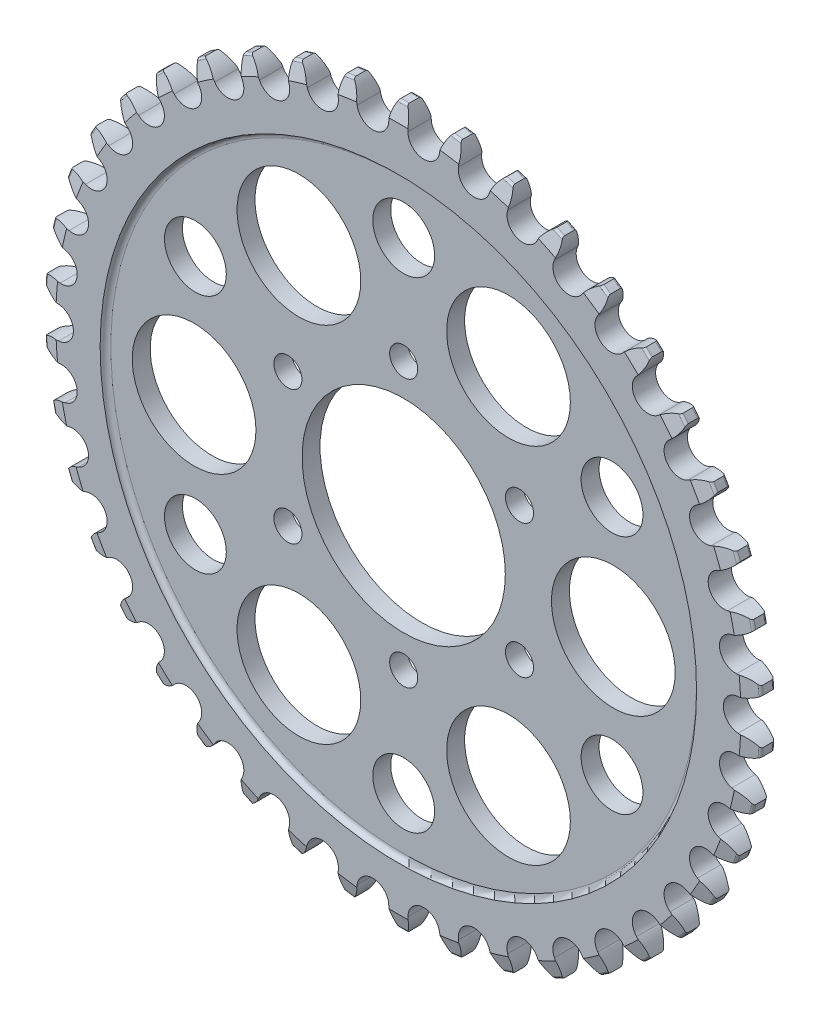
SolidWorks part; units mm, degrees
ref_plane "Front" through (0, 0, 0) normal (0, 0, 1) x (1, 0, 0)
ref_plane "Top" through (0, 0, 0) normal (0, 1, 0) x (1, 0, 0)
ref_plane "Right" through (0, 0, 0) normal (1, 0, 0) x (0, 0, -1)
sketch "Sketch1" plane through (0, 0, 0) normal (0, 0, 1) x (1, 0, 0)
  line L0 (0, 0) -> (0, 165.4268) construction
  line L1 (0, 0) -> (24.4609, 162.2874) construction
  line L2 (0, 0) -> (-25.1185, 166.6504) construction
  line L3 (-9.525, 0) -> (-9.525, 165.4268) construction
  line L4 (9.525, 0) -> (9.525, 163.4542) construction
  line L5 (-9.525, 0) -> (-9.525, 27.2747) construction
  line L6 (9.525, 0) -> (9.525, 27.2747) construction
  line L7 (0, 0) -> (0, 27.2747) construction
  line L8 (9.4186, 1.4196) -> (-15.3101, 165.4838) construction
  line L9 (-9.4186, 1.4196) -> (15.1489, 164.4141) construction
  line L10 (0, 0) -> (11.7596, 78.0201) construction
  line L11 (-9.4186, 1.4196) -> (2.341, 79.4398) construction
  line L12 (9.4186, 1.4196) -> (-9.2498, 125.2762) construction
  line L13 (0, 0) -> (-18.6684, 123.8565) construction
  line L14 (-9.525, 127.1023) -> (9.525, 127.1023) construction
  line L15 (0, 0) -> (60.5367, 104.8526) construction
  line L16 (0, 0) -> (123.9656, 71.5716) construction
  arc A0 (-9.525, 121.1492) -> (-3.5719, 127.1023) centre (-9.525, 127.1023) ccw
  circle A1 centre (0, 0) radius 111.5056
  arc A2 (3.5719, 127.1023) -> (8.6377, 121.2157) centre (9.525, 127.1023) ccw
  arc A3 (0, 136.0913) -> (-3.5719, 127.1023) centre (9.525, 127.1023) ccw
  circle A4 centre (0, 0) radius 101.5056 construction
  arc A5 (3.5719, 127.1023) -> (0, 136.0913) centre (-9.525, 127.1023) ccw
  circle A6 centre (0, 0) radius 38
  circle A7 centre (0, 0) radius 50 construction
  circle A8 centre (0, 50) radius 5.25
  circle A9 centre (0, 0) radius 55.25 construction
  circle A10 centre (39.1889, 67.8772) radius 23.1278
  circle A11 centre (77.8918, 44.9708) radius 11.5639
  circle A12 centre (0, 0) radius 78.3778 construction
  circle A13 centre (43.3013, 25) radius 5.25
  circle A14 centre (78.3778, 0) radius 23.1278
  circle A15 centre (77.8918, -44.9708) radius 11.5639
  circle A16 centre (43.3013, -25) radius 5.25
  circle A17 centre (39.1889, -67.8772) radius 23.1278
  circle A18 centre (0, -89.9417) radius 11.5639
  circle A19 centre (0, -50) radius 5.25
  circle A20 centre (-39.1889, -67.8772) radius 23.1278
  circle A21 centre (-77.8918, -44.9708) radius 11.5639
  circle A22 centre (-43.3013, -25) radius 5.25
  circle A23 centre (-78.3778, 0) radius 23.1278
  circle A24 centre (-77.8918, 44.9708) radius 11.5639
  circle A25 centre (-43.3013, 25) radius 5.25
  circle A26 centre (-39.1889, 67.8772) radius 23.1278
  circle A27 centre (0, 89.9417) radius 11.5639
  arc A28 (8.6377, 121.2157) -> (15.4116, 126.215) centre (9.525, 127.1023) ccw
  arc A29 (20.2834, 134.5713) -> (15.4116, 126.215) centre (28.3622, 124.263) ccw
  arc A30 (22.4756, 125.1503) -> (20.2834, 134.5713) centre (9.525, 127.1023) ccw
  arc A31 (22.4756, 125.1503) -> (26.6075, 118.5744) centre (28.3622, 124.263) ccw
  arc A32 (26.6075, 118.5744) -> (34.0509, 122.5083) centre (28.3622, 124.263) ccw
  arc A33 (40.1136, 130.0452) -> (34.0509, 122.5083) centre (46.5659, 118.648) ccw
  arc A34 (40.8772, 120.4027) -> (40.1136, 130.0452) centre (28.3622, 124.263) ccw
  arc A35 (40.8772, 120.4027) -> (43.9829, 113.2844) centre (46.5659, 118.648) ccw
  arc A36 (43.9829, 113.2844) -> (51.9295, 116.065) centre (46.5659, 118.648) ccw
  arc A37 (59.0478, 122.614) -> (51.9295, 116.065) centre (63.7293, 110.3825) ccw
  arc A38 (58.3658, 112.9654) -> (59.0478, 122.614) centre (46.5659, 118.648) ccw
  arc A39 (58.3658, 112.9654) -> (60.3758, 105.4638) centre (63.7293, 110.3825) ccw
  arc A40 (60.3758, 105.4638) -> (68.648, 107.029) centre (63.7293, 110.3825) ccw
  arc A41 (76.663, 112.4439) -> (68.648, 107.029) centre (79.4692, 99.6512) ccw
  arc A42 (74.5505, 103.0047) -> (76.663, 112.4439) centre (63.7293, 110.3825) ccw
  arc A43 (74.5505, 103.0047) -> (75.42, 95.2873) centre (79.4692, 99.6512) ccw
  arc A44 (75.42, 95.2873) -> (83.8331, 95.6021) centre (79.4692, 99.6512) ccw
  arc A45 (92.5656, 99.762) -> (83.8331, 95.6021) centre (93.4338, 86.6939) ccw
  arc A46 (89.0699, 90.7431) -> (92.5656, 99.762) centre (79.4692, 99.6512) ccw
  arc A47 (89.0699, 90.7431) -> (88.7795, 82.9822) centre (93.4338, 86.6939) ccw
  arc A48 (88.7795, 82.9822) -> (97.1455, 82.0396) centre (93.4338, 86.6939) ccw
  arc A49 (106.4005, 84.8515) -> (97.1455, 82.0396) centre (105.3113, 71.8) ccw
  arc A50 (101.5996, 76.4544) -> (106.4005, 84.8515) centre (93.4338, 86.6939) ccw
  arc A51 (101.5996, 76.4544) -> (100.1558, 68.8235) centre (105.3113, 71.8) ccw
  arc A52 (100.1558, 68.8235) -> (108.2879, 66.6445) centre (105.3113, 71.8) ccw
  arc A53 (117.8585, 68.0457) -> (108.2879, 66.6445) centre (114.8363, 55.3023) ccw
  arc A54 (111.8598, 60.4578) -> (117.8585, 68.0457) centre (105.3113, 71.8) ccw
  arc A55 (111.8598, 60.4578) -> (109.2947, 53.1273) centre (114.8363, 55.3023) ccw
  arc A56 (109.2947, 53.1273) -> (117.0112, 49.7606) centre (114.8363, 55.3023) ccw
  arc A57 (126.6838, 49.7197) -> (117.0112, 49.7606) centre (121.7961, 37.5691) ccw
  arc A58 (119.6211, 43.1107) -> (126.6838, 49.7197) centre (114.8363, 55.3023) ccw
  arc A59 (119.6211, 43.1107) -> (115.9922, 36.2444) centre (121.7961, 37.5691) ccw
  arc A60 (115.9922, 36.2444) -> (123.1208, 31.7652) centre (121.7961, 37.5691) ccw
  arc A61 (132.6792, 30.2832) -> (123.1208, 31.7652) centre (126.0351, 18.9967) ccw
  arc A62 (124.7104, 24.8006) -> (132.6792, 30.2832) centre (121.7961, 37.5691) ccw
  arc A63 (124.7104, 24.8006) -> (120.0986, 18.5519) centre (126.0351, 18.9967) ccw
  arc A64 (120.0986, 18.5519) -> (126.48, 13.0603) centre (126.0351, 18.9967) ccw
  arc A65 (135.7108, 10.1701) -> (126.48, 13.0603) centre (127.4587, 0) ccw
  arc A66 (127.0138, 5.9365) -> (135.7108, 10.1701) centre (126.0351, 18.9967) ccw
  arc A67 (127.0138, 5.9365) -> (121.5222, 0.4449) centre (127.4587, 0) ccw
  arc A68 (121.5222, 0.4449) -> (127.0138, -5.9365) centre (127.4587, 0) ccw
  arc A69 (135.7108, -10.1701) -> (127.0138, -5.9365) centre (126.0351, -18.9967) ccw
  arc A70 (126.48, -13.0603) -> (135.7108, -10.1701) centre (127.4587, 0) ccw
  arc A71 (126.48, -13.0603) -> (120.2312, -17.672) centre (126.0351, -18.9967) ccw
  arc A72 (120.2312, -17.672) -> (124.7104, -24.8006) centre (126.0351, -18.9967) ccw
  arc A73 (132.6792, -30.2832) -> (124.7104, -24.8006) centre (121.7961, -37.5691) ccw
  arc A74 (123.1208, -31.7652) -> (132.6792, -30.2832) centre (126.0351, -18.9967) ccw
  arc A75 (123.1208, -31.7652) -> (116.2545, -35.3942) centre (121.7961, -37.5691) ccw
  arc A76 (116.2545, -35.3942) -> (119.6211, -43.1107) centre (121.7961, -37.5691) ccw
  arc A77 (126.6838, -49.7197) -> (119.6211, -43.1107) centre (114.8363, -55.3023) ccw
  arc A78 (117.0112, -49.7606) -> (126.6838, -49.7197) centre (121.7961, -37.5691) ccw
  arc A79 (117.0112, -49.7606) -> (109.6808, -52.3257) centre (114.8363, -55.3023) ccw
  arc A80 (109.6808, -52.3257) -> (111.8598, -60.4578) centre (114.8363, -55.3023) ccw
  arc A81 (117.8585, -68.0457) -> (111.8598, -60.4578) centre (105.3113, -71.8) ccw
  arc A82 (108.2879, -66.6445) -> (117.8585, -68.0457) centre (114.8363, -55.3023) ccw
  arc A83 (108.2879, -66.6445) -> (100.657, -68.0883) centre (105.3113, -71.8) ccw
  arc A84 (100.657, -68.0883) -> (101.5996, -76.4544) centre (105.3113, -71.8) ccw
  arc A85 (106.4005, -84.8515) -> (101.5996, -76.4544) centre (93.4338, -86.6939) ccw
  arc A86 (97.1455, -82.0396) -> (106.4005, -84.8515) centre (105.3113, -71.8) ccw
  arc A87 (97.1455, -82.0396) -> (89.3847, -82.33) centre (93.4338, -86.6939) ccw
  arc A88 (89.3847, -82.33) -> (89.0699, -90.7431) centre (93.4338, -86.6939) ccw
  arc A89 (92.5656, -99.762) -> (89.0699, -90.7431) centre (79.4692, -99.6512) ccw
  arc A90 (83.8331, -95.6021) -> (92.5656, -99.762) centre (93.4338, -86.6939) ccw
  arc A91 (83.8331, -95.6021) -> (76.1157, -94.7325) centre (79.4692, -99.6512) ccw
  arc A92 (76.1157, -94.7325) -> (74.5505, -103.0047) centre (79.4692, -99.6512) ccw
  arc A93 (76.663, -112.4439) -> (74.5505, -103.0047) centre (63.7293, -110.3825) ccw
  arc A94 (68.648, -107.029) -> (76.663, -112.4439) centre (79.4692, -99.6512) ccw
  arc A95 (68.648, -107.029) -> (61.1464, -105.0189) centre (63.7293, -110.3825) ccw
  arc A96 (61.1464, -105.0189) -> (58.3658, -112.9654) centre (63.7293, -110.3825) ccw
  arc A97 (59.0478, -122.614) -> (58.3658, -112.9654) centre (46.5659, -118.648) ccw
  arc A98 (51.9295, -116.065) -> (59.0478, -122.614) centre (63.7293, -110.3825) ccw
  arc A99 (51.9295, -116.065) -> (44.8112, -112.9593) centre (46.5659, -118.648) ccw
  arc A100 (44.8112, -112.9593) -> (40.8772, -120.4027) centre (46.5659, -118.648) ccw
  arc A101 (40.1136, -130.0452) -> (40.8772, -120.4027) centre (28.3622, -124.263) ccw
  arc A102 (34.0509, -122.5083) -> (40.1136, -130.0452) centre (46.5659, -118.648) ccw
  arc A103 (34.0509, -122.5083) -> (27.475, -118.3764) centre (28.3622, -124.263) ccw
  arc A104 (27.475, -118.3764) -> (22.4756, -125.1503) centre (28.3622, -124.263) ccw
  arc A105 (20.2834, -134.5713) -> (22.4756, -125.1503) centre (9.525, -127.1023) ccw
  arc A106 (15.4116, -126.215) -> (20.2834, -134.5713) centre (28.3622, -124.263) ccw
  arc A107 (15.4116, -126.215) -> (9.525, -121.1492) centre (9.525, -127.1023) ccw
  arc A108 (9.525, -121.1492) -> (3.5719, -127.1023) centre (9.525, -127.1023) ccw
  arc A109 (0, -136.0913) -> (3.5719, -127.1023) centre (-9.525, -127.1023) ccw
  arc A110 (-3.5719, -127.1023) -> (0, -136.0913) centre (9.525, -127.1023) ccw
  arc A111 (-3.5719, -127.1023) -> (-8.6377, -121.2157) centre (-9.525, -127.1023) ccw
  arc A112 (-8.6377, -121.2157) -> (-15.4116, -126.215) centre (-9.525, -127.1023) ccw
  arc A113 (-20.2834, -134.5713) -> (-15.4116, -126.215) centre (-28.3622, -124.263) ccw
  arc A114 (-22.4756, -125.1503) -> (-20.2834, -134.5713) centre (-9.525, -127.1023) ccw
  arc A115 (-22.4756, -125.1503) -> (-26.6075, -118.5744) centre (-28.3622, -124.263) ccw
  arc A116 (-26.6075, -118.5744) -> (-34.0509, -122.5083) centre (-28.3622, -124.263) ccw
  arc A117 (-40.1136, -130.0452) -> (-34.0509, -122.5083) centre (-46.5659, -118.648) ccw
  arc A118 (-40.8772, -120.4027) -> (-40.1136, -130.0452) centre (-28.3622, -124.263) ccw
  arc A119 (-40.8772, -120.4027) -> (-43.9829, -113.2844) centre (-46.5659, -118.648) ccw
  arc A120 (-43.9829, -113.2844) -> (-51.9295, -116.065) centre (-46.5659, -118.648) ccw
  arc A121 (-59.0478, -122.614) -> (-51.9295, -116.065) centre (-63.7293, -110.3825) ccw
  arc A122 (-58.3658, -112.9654) -> (-59.0478, -122.614) centre (-46.5659, -118.648) ccw
  arc A123 (-58.3658, -112.9654) -> (-60.3758, -105.4638) centre (-63.7293, -110.3825) ccw
  arc A124 (-60.3758, -105.4638) -> (-68.648, -107.029) centre (-63.7293, -110.3825) ccw
  arc A125 (-76.663, -112.4439) -> (-68.648, -107.029) centre (-79.4692, -99.6512) ccw
  arc A126 (-74.5505, -103.0047) -> (-76.663, -112.4439) centre (-63.7293, -110.3825) ccw
  arc A127 (-74.5505, -103.0047) -> (-75.42, -95.2873) centre (-79.4692, -99.6512) ccw
  arc A128 (-75.42, -95.2873) -> (-83.8331, -95.6021) centre (-79.4692, -99.6512) ccw
  arc A129 (-92.5656, -99.762) -> (-83.8331, -95.6021) centre (-93.4338, -86.6939) ccw
  arc A130 (-89.0699, -90.7431) -> (-92.5656, -99.762) centre (-79.4692, -99.6512) ccw
  arc A131 (-89.0699, -90.7431) -> (-88.7795, -82.9822) centre (-93.4338, -86.6939) ccw
  arc A132 (-88.7795, -82.9822) -> (-97.1455, -82.0396) centre (-93.4338, -86.6939) ccw
  arc A133 (-106.4005, -84.8515) -> (-97.1455, -82.0396) centre (-105.3113, -71.8) ccw
  arc A134 (-101.5996, -76.4544) -> (-106.4005, -84.8515) centre (-93.4338, -86.6939) ccw
  arc A135 (-101.5996, -76.4544) -> (-100.1558, -68.8235) centre (-105.3113, -71.8) ccw
  arc A136 (-100.1558, -68.8235) -> (-108.2879, -66.6445) centre (-105.3113, -71.8) ccw
  arc A137 (-117.8585, -68.0457) -> (-108.2879, -66.6445) centre (-114.8363, -55.3023) ccw
  arc A138 (-111.8598, -60.4578) -> (-117.8585, -68.0457) centre (-105.3113, -71.8) ccw
  arc A139 (-111.8598, -60.4578) -> (-109.2947, -53.1273) centre (-114.8363, -55.3023) ccw
  arc A140 (-109.2947, -53.1273) -> (-117.0112, -49.7606) centre (-114.8363, -55.3023) ccw
  arc A141 (-126.6838, -49.7197) -> (-117.0112, -49.7606) centre (-121.7961, -37.5691) ccw
  arc A142 (-119.6211, -43.1107) -> (-126.6838, -49.7197) centre (-114.8363, -55.3023) ccw
  arc A143 (-119.6211, -43.1107) -> (-115.9922, -36.2444) centre (-121.7961, -37.5691) ccw
  arc A144 (-115.9922, -36.2444) -> (-123.1208, -31.7652) centre (-121.7961, -37.5691) ccw
  arc A145 (-132.6792, -30.2832) -> (-123.1208, -31.7652) centre (-126.0351, -18.9967) ccw
  arc A146 (-124.7104, -24.8006) -> (-132.6792, -30.2832) centre (-121.7961, -37.5691) ccw
  arc A147 (-124.7104, -24.8006) -> (-120.0986, -18.5519) centre (-126.0351, -18.9967) ccw
  arc A148 (-120.0986, -18.5519) -> (-126.48, -13.0603) centre (-126.0351, -18.9967) ccw
  arc A149 (-135.7108, -10.1701) -> (-126.48, -13.0603) centre (-127.4587, 0) ccw
  arc A150 (-127.0138, -5.9365) -> (-135.7108, -10.1701) centre (-126.0351, -18.9967) ccw
  arc A151 (-127.0138, -5.9365) -> (-121.5222, -0.4449) centre (-127.4587, 0) ccw
  arc A152 (-121.5222, -0.4449) -> (-127.0138, 5.9365) centre (-127.4587, 0) ccw
  arc A153 (-135.7108, 10.1701) -> (-127.0138, 5.9365) centre (-126.0351, 18.9967) ccw
  arc A154 (-126.48, 13.0603) -> (-135.7108, 10.1701) centre (-127.4587, 0) ccw
  arc A155 (-126.48, 13.0603) -> (-120.2312, 17.672) centre (-126.0351, 18.9967) ccw
  arc A156 (-120.2312, 17.672) -> (-124.7104, 24.8006) centre (-126.0351, 18.9967) ccw
  arc A157 (-132.6792, 30.2832) -> (-124.7104, 24.8006) centre (-121.7961, 37.5691) ccw
  arc A158 (-123.1208, 31.7652) -> (-132.6792, 30.2832) centre (-126.0351, 18.9967) ccw
  arc A159 (-123.1208, 31.7652) -> (-116.2545, 35.3942) centre (-121.7961, 37.5691) ccw
  arc A160 (-116.2545, 35.3942) -> (-119.6211, 43.1107) centre (-121.7961, 37.5691) ccw
  arc A161 (-126.6838, 49.7197) -> (-119.6211, 43.1107) centre (-114.8363, 55.3023) ccw
  arc A162 (-117.0112, 49.7606) -> (-126.6838, 49.7197) centre (-121.7961, 37.5691) ccw
  arc A163 (-117.0112, 49.7606) -> (-109.6808, 52.3257) centre (-114.8363, 55.3023) ccw
  arc A164 (-109.6808, 52.3257) -> (-111.8598, 60.4578) centre (-114.8363, 55.3023) ccw
  arc A165 (-117.8585, 68.0457) -> (-111.8598, 60.4578) centre (-105.3113, 71.8) ccw
  arc A166 (-108.2879, 66.6445) -> (-117.8585, 68.0457) centre (-114.8363, 55.3023) ccw
  arc A167 (-108.2879, 66.6445) -> (-100.657, 68.0883) centre (-105.3113, 71.8) ccw
  arc A168 (-100.657, 68.0883) -> (-101.5996, 76.4544) centre (-105.3113, 71.8) ccw
  arc A169 (-106.4005, 84.8515) -> (-101.5996, 76.4544) centre (-93.4338, 86.6939) ccw
  arc A170 (-97.1455, 82.0396) -> (-106.4005, 84.8515) centre (-105.3113, 71.8) ccw
  arc A171 (-97.1455, 82.0396) -> (-89.3847, 82.33) centre (-93.4338, 86.6939) ccw
  arc A172 (-89.3847, 82.33) -> (-89.0699, 90.7431) centre (-93.4338, 86.6939) ccw
  arc A173 (-92.5656, 99.762) -> (-89.0699, 90.7431) centre (-79.4692, 99.6512) ccw
  arc A174 (-83.8331, 95.6021) -> (-92.5656, 99.762) centre (-93.4338, 86.6939) ccw
  arc A175 (-83.8331, 95.6021) -> (-76.1157, 94.7325) centre (-79.4692, 99.6512) ccw
  arc A176 (-76.1157, 94.7325) -> (-74.5505, 103.0047) centre (-79.4692, 99.6512) ccw
  arc A177 (-76.663, 112.4439) -> (-74.5505, 103.0047) centre (-63.7293, 110.3825) ccw
  arc A178 (-68.648, 107.029) -> (-76.663, 112.4439) centre (-79.4692, 99.6512) ccw
  arc A179 (-68.648, 107.029) -> (-61.1464, 105.0189) centre (-63.7293, 110.3825) ccw
  arc A180 (-61.1464, 105.0189) -> (-58.3658, 112.9654) centre (-63.7293, 110.3825) ccw
  arc A181 (-59.0478, 122.614) -> (-58.3658, 112.9654) centre (-46.5659, 118.648) ccw
  arc A182 (-51.9295, 116.065) -> (-59.0478, 122.614) centre (-63.7293, 110.3825) ccw
  arc A183 (-51.9295, 116.065) -> (-44.8112, 112.9593) centre (-46.5659, 118.648) ccw
  arc A184 (-44.8112, 112.9593) -> (-40.8772, 120.4027) centre (-46.5659, 118.648) ccw
  arc A185 (-40.1136, 130.0452) -> (-40.8772, 120.4027) centre (-28.3622, 124.263) ccw
  arc A186 (-34.0509, 122.5083) -> (-40.1136, 130.0452) centre (-46.5659, 118.648) ccw
  arc A187 (-34.0509, 122.5083) -> (-27.475, 118.3764) centre (-28.3622, 124.263) ccw
  arc A188 (-27.475, 118.3764) -> (-22.4756, 125.1503) centre (-28.3622, 124.263) ccw
  arc A189 (-20.2834, 134.5713) -> (-22.4756, 125.1503) centre (-9.525, 127.1023) ccw
  arc A190 (-15.4116, 126.215) -> (-20.2834, 134.5713) centre (-28.3622, 124.263) ccw
  arc A191 (-15.4116, 126.215) -> (-9.525, 121.1492) centre (-9.525, 127.1023) ccw
  point P78 (0, 0)
  point P321 (0, 0)
  point P366 (0, 0)
  dimension "D7" = 11.9062
  dimension "D9" = 10
  dimension "D10" = 10
  dimension "D11" = 10.5
  dimension "D12" = 100
  dimension "D13" = 76
  dimension "D1" = 8.571
  dimension "D2" = 8.571
  dimension "D8" = 19.05
  dimension "D14" = 30
  dimension "D15" = 30
  dimension "D3" = 9.525
  dimension "D4" = 9.525
  dimension "D5" = 9.525
  dimension "D6" = 9.525
  dimension "D16" = 6
  dimension "D17" = 42
extrude "Boss-Extrude1" add sketch "Sketch1" along normal mid plane 8.7122 contours A1 A27 A26 A25 A24 A23 A22 A21 A20 A19 A18 A17 A16 A15 A14 A13 A11 A10 A8 A6 | A191 A190 A189 A188 A187 A186 A185 A184 A183 A182 A181 A180 A179 A178 A177 A176 A175 A174 A173 A172 A171 A170 A169 A168 A167 A166 A165 A164 A163 A162 A161 A160 A159 A158 A157 A156 A155 A154 A153 A152 A151 A150 A149 A148 A147 A146 A145 A144 A143 A142 A141 region at (-2.5975, 120.1748, 0) region at (-108.3517, 0, 0)
extrude "Cut-Extrude1" cut sketch "Sketch1<3>" against normal blind 2 from surface contours A1 A27 A26 A25 A24 A23 A22 A21 A20 A19 A18 A17 A16 A15 A14 A13 A11 A10 A8 A6 region at (-108.3517, 0, 0) starting at face at (11.5639, 89.9417, 4.3561)
sketch "Sketch1<3>" plane through (0, 0, 0) normal (0, 0, 1) x (1, 0, 0) same geometry as "Sketch1"
fillet "Fillet1" radius 2 1 edges at (111.5056, 0, 2.3561)
sketch "Sketch2" plane through (0, 0, 0) normal (1, 0, 0) x (0, 0, -1)
  line L0 (-4.3561, 0) -> (4.3561, 0) construction
  line L1 (-4.3561, 5.9365) -> (-4.3561, -5.9365) construction
  line L2 (4.3561, -5.9365) -> (4.3561, 5.9365) construction
  line L3 (-4.3561, 136.0913) -> (4.3561, 136.0913)
  line L4 (4.3561, 136.0913) -> (4.3561, 127.9398)
  line L5 (4.3561, 120.4027) -> (4.3561, 130.0452) construction
  line L6 (4.3561, 127.9398) -> (2.707, 133.3813)
  line L7 (1.75, 134.0913) -> (-1.75, 134.0913)
  line L8 (-2.7047, 133.3889) -> (-4.3561, 128.0913)
  line L9 (-4.3561, 130.0452) -> (-4.3561, 120.4027) construction
  line L10 (-4.3561, 128.0913) -> (-4.3561, 136.0913)
  line L11 (0, 136.0913) -> (0, 134.0913) construction
  arc A0 (2.707, 133.3813) -> (1.75, 134.0913) centre (1.75, 133.0913) ccw
  arc A1 (-1.75, 134.0913) -> (-2.7047, 133.3889) centre (-1.75, 133.0913) ccw
  dimension "D3" = 1
  dimension "D1" = 8
  dimension "D2" = 2
  dimension "D4" = 3.5
revolve "Cut-Revolve1" cut sketch "Sketch2" angle 360 about L0
scale "Scale1" scale about centroid uniform scaling yes scale factor 0.3
